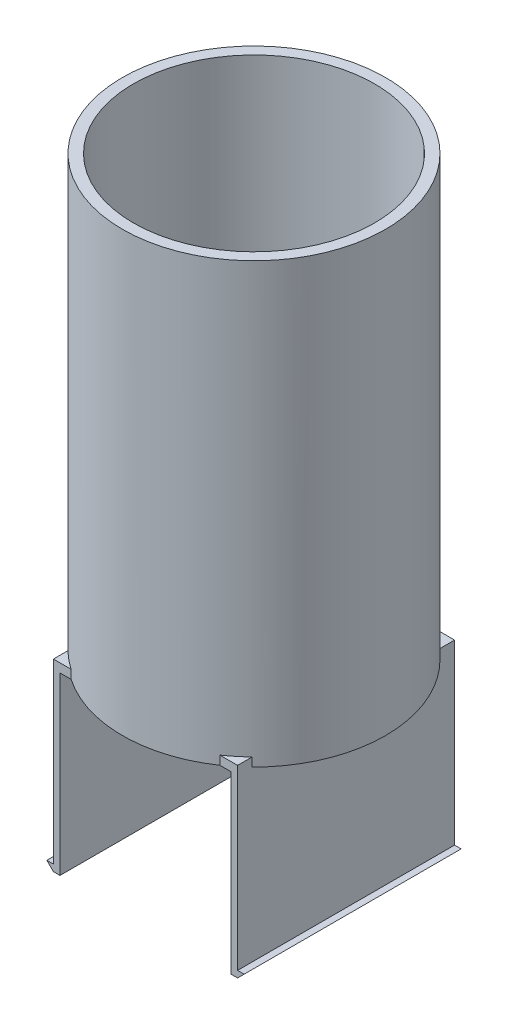
SolidWorks part; units mm, degrees
ref_plane "Front Plane" through (0, 0, 0) normal (0, 0, 1) x (1, 0, 0)
ref_plane "Top Plane" through (0, 0, 0) normal (0, 1, 0) x (1, 0, 0)
ref_plane "Right Plane" through (0, 0, 0) normal (1, 0, 0) x (0, 0, -1)
sketch "Sketch1" plane through (0, 0, 0) normal (0, 1, 0) x (1, 0, 0)
  circle A0 centre (0, 0) radius 27.5
  circle A1 centre (0, 0) radius 30
  dimension "D1" = 55
  dimension "D2" = 60
extrude "Boss-Extrude1" add sketch "Sketch1" along normal blind 100
extrude "Boss-Extrude2" add sketch "Sketch1<2>" along normal blind 5 contours A0 region at (0, 0, 0)
sketch "Sketch1<2>" plane through (0, 0, 0) normal (0, 1, 0) x (1, 0, 0) same geometry as "Sketch1"
sketch "Sketch2" plane through (0, 0, 0) normal (0, -1, 0) x (1, 0, 0)
  line L1 (-19.5, 24.75) -> (-21, 24.75)
  line L2 (-19.5, 24.75) -> (-19.5, -24.75)
  line L3 (-19.5, -24.75) -> (-21, -24.75)
  line L4 (-21, 24.75) -> (-21, -24.75)
  line L5 (21, 24.75) -> (19.5, 24.75)
  line L6 (21, 24.75) -> (21, -24.75)
  line L7 (21, -24.75) -> (19.5, -24.75)
  line L8 (19.5, 24.75) -> (19.5, -24.75)
  circle A0 centre (0, 0) radius 30 construction
  point P8 (-20.25, 24.75)
  dimension "D1" = 1.5
  dimension "D2" = 42
  dimension "D3" = 21
  dimension "D4" = 49.5
  dimension "D5" = 24.75
extrude "Boss-Extrude3" add sketch "Sketch2" along normal blind 40
sketch "Sketch3" plane through (0, 0, 0) normal (0, -1, 0) x (1, 0, 0)
  line L1 (21, 24.75) -> (-21, 24.75)
  line L2 (21, 24.75) -> (21, -24.75)
  line L3 (21, -24.75) -> (-21, -24.75)
  line L4 (-21, 24.75) -> (-21, -24.75)
extrude "Boss-Extrude4" add sketch "Sketch3" against normal blind 2
sketch "Sketch4" plane through (0, 0, -24.75) normal (0, 0, -1) x (-1, 0, 0)
  line L0 (21, -40) -> (22.5, -38.5)
  line L1 (22.5, -38.5) -> (21, -38.5)
  line L2 (21, -40) -> (21, 2) construction
  line L3 (21, -38.5) -> (21, -40)
  line L4 (-21, -40) -> (-22.5, -38.5)
  line L5 (-22.5, -38.5) -> (-21, -38.5)
  line L6 (-21, -40) -> (-21, 2) construction
  line L7 (-21, -38.5) -> (-21, -40)
  dimension "D1" = 45
  dimension "D2" = 45
  dimension "D3" = 1.5
  dimension "D4" = 1.5
extrude "Boss-Extrude5" add sketch "Sketch4" against normal up to surface (49.5 mm away) up to face at (19.1513, -12.6667, 24.75)
